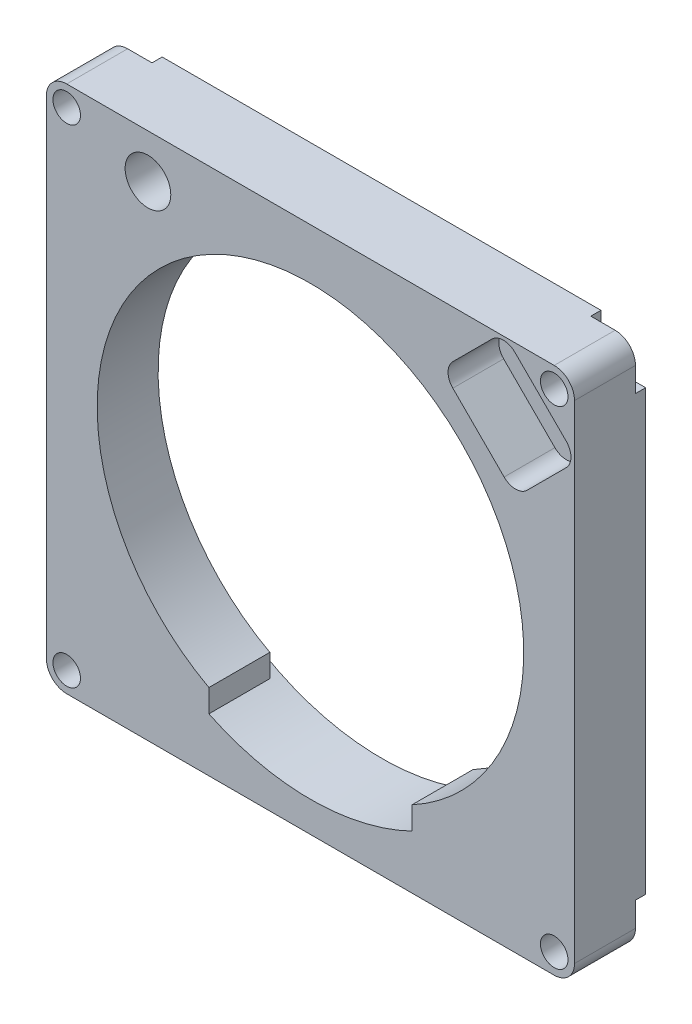
SolidWorks part; units mm, degrees
material "PET"
ref_plane "Front Plane" through (0, 0, 0) normal (0, 0, 1) x (1, 0, 0)
ref_plane "Top Plane" through (0, 0, 0) normal (0, 1, 0) x (1, 0, 0)
ref_plane "Right Plane" through (0, 0, 0) normal (1, 0, 0) x (0, 0, -1)
sketch "Sketch1" plane through (0, 0, 0) normal (0, 0, 1) x (1, 0, 0)
  line L4 (-38.1, -41.275) -> (38.1, -41.275)
  line L5 (41.275, -38.1) -> (41.275, 38.1)
  line L6 (38.1, 41.275) -> (-38.1, 41.275)
  line L7 (-41.275, 38.1) -> (-41.275, -38.1)
  line L8 (-38.1, -41.275) -> (38.1, -41.275)
  line L9 (41.275, -38.1) -> (41.275, 38.1)
  line L10 (38.1, 41.275) -> (-38.1, 41.275)
  line L11 (-41.275, 38.1) -> (-41.275, -38.1)
  line L388 (15.875, -29.3151) -> (15.875, -32.8808) construction
  line L389 (-15.875, -32.8808) -> (-15.875, -29.3151) construction
  line L390 (15.875, -29.3151) -> (15.875, -32.8808)
  line L391 (-15.875, -32.8808) -> (-15.875, -29.3151)
  arc A4 (-41.275, -38.1) -> (-38.1, -41.275) centre (-38.1, -38.1) ccw
  arc A5 (38.1, -41.275) -> (41.275, -38.1) centre (38.1, -38.1) ccw
  arc A6 (41.275, 38.1) -> (38.1, 41.275) centre (38.1, 38.1) ccw
  arc A7 (-38.1, 41.275) -> (-41.275, 38.1) centre (-38.1, 38.1) ccw
  arc A8 (-41.275, -38.1) -> (-38.1, -41.275) centre (-38.1, -38.1) ccw
  arc A9 (38.1, -41.275) -> (41.275, -38.1) centre (38.1, -38.1) ccw
  arc A10 (41.275, 38.1) -> (38.1, 41.275) centre (38.1, 38.1) ccw
  arc A11 (-38.1, 41.275) -> (-41.275, 38.1) centre (-38.1, 38.1) ccw
  arc A388 (15.875, -29.3151) -> (-15.875, -29.3151) centre (0, 0) ccw construction
  arc A389 (-15.875, -32.8808) -> (15.875, -32.8808) centre (0, 0) ccw construction
  arc A390 (15.875, -29.3151) -> (-15.875, -29.3151) centre (0, 0) ccw
  arc A391 (-15.875, -32.8808) -> (15.875, -32.8808) centre (0, 0) ccw
  dimension "D1" = 0
extrude "Boss-Extrude1" add sketch "Sketch1" against normal up to surface (7.9375 mm away)
sketch "Sketch2" plane through (0, 0, -7.9375) normal (0, 0, -1) x (-1, 0, 0)
  line L12 (-34.29, -38.1) -> (-34.29, -41.275)
  line L13 (-34.29, -41.275) -> (34.29, -41.275)
  line L14 (34.29, -41.275) -> (34.29, -38.1)
  line L15 (38.1, -34.29) -> (41.275, -34.29)
  line L16 (41.275, -34.29) -> (41.275, 34.29)
  line L17 (41.275, 34.29) -> (38.1, 34.29)
  line L18 (34.29, 38.1) -> (34.29, 41.275)
  line L19 (34.29, 41.275) -> (-34.29, 41.275)
  line L20 (-34.29, 41.275) -> (-34.29, 38.1)
  line L21 (-38.1, 34.29) -> (-41.275, 34.29)
  line L22 (-41.275, 34.29) -> (-41.275, -34.29)
  line L23 (-41.275, -34.29) -> (-38.1, -34.29)
  line L24 (-34.29, -38.1) -> (-34.29, -41.275)
  line L25 (-34.29, -41.275) -> (34.29, -41.275)
  line L26 (34.29, -41.275) -> (34.29, -38.1)
  line L27 (38.1, -34.29) -> (41.275, -34.29)
  line L28 (41.275, -34.29) -> (41.275, 34.29)
  line L29 (41.275, 34.29) -> (38.1, 34.29)
  line L30 (34.29, 38.1) -> (34.29, 41.275)
  line L31 (34.29, 41.275) -> (-34.29, 41.275)
  line L32 (-34.29, 41.275) -> (-34.29, 38.1)
  line L33 (-38.1, 34.29) -> (-41.275, 34.29)
  line L34 (-41.275, 34.29) -> (-41.275, -34.29)
  line L35 (-41.275, -34.29) -> (-38.1, -34.29)
  circle A0 centre (0, 0) radius 36.5125 construction
  circle A1 centre (0, 0) radius 36.5125
  arc A4 (-34.29, -38.1) -> (-38.1, -34.29) centre (-38.1, -38.1) ccw
  arc A5 (38.1, -34.29) -> (34.29, -38.1) centre (38.1, -38.1) ccw
  arc A6 (34.29, 38.1) -> (38.1, 34.29) centre (38.1, 38.1) ccw
  arc A7 (-38.1, 34.29) -> (-34.29, 38.1) centre (-38.1, 38.1) ccw
  arc A8 (-34.29, -38.1) -> (-38.1, -34.29) centre (-38.1, -38.1) ccw
  arc A9 (38.1, -34.29) -> (34.29, -38.1) centre (38.1, -38.1) ccw
  arc A10 (34.29, 38.1) -> (38.1, 34.29) centre (38.1, 38.1) ccw
  arc A11 (-38.1, 34.29) -> (-34.29, 38.1) centre (-38.1, 38.1) ccw
  dimension "D1" = 0
extrude "Boss-Extrude2" add sketch "Sketch2" along normal blind 1.5875
hole_wizard "#6 Clearance Hole1" positions "Sketch4" profile "Sketch3" hole size "#6" standard "ANSI Inch" end condition through all
sketch "Sketch4" plane through (0, 0, -7.9375) normal (0, 0, -1) x (-1, 0, 0)
  point P0 (-38.1, 38.1)
  point P3 (38.1, 38.1)
  point P6 (38.1, -38.1)
  point P9 (-38.1, -38.1)
sketch "Sketch3" plane through (38.1, 38.1, -7.9375) normal (1, 0, 0) x (0, 1, 0)
  line L0 (0, 0) -> (0, 7.9375)
  line L1 (0, 7.9375) -> (2.1526, 7.9375)
  line L2 (2.1526, 7.9375) -> (2.1526, 0)
  line L5 (2.1526, 0) -> (0, 0)
  line L11 (0, -6.35) -> (0, 107.95) construction
  dimension "Thru Hole Dia." = 4.3053
  dimension "Thru Hole Depth" = 7.9375
sketch "Sketch5" plane through (0, 0, 0) normal (0, 0, 1) x (1, 0, 0)
  circle A0 centre (-25.4, 34.417) radius 3.5712
  dimension "D1" = 7.1425
extrude "Cut-Extrude1" cut sketch "Sketch5" against normal offset from surface (7.9375 mm away) 1.5875 up to face at (0, 0, -9.525)
sketch "Sketch6" plane through (0, 0, -7.9375) normal (0, 0, 1) x (1, 0, 0)
  circle A0 centre (-25.4, 34.417) radius 2.1
  dimension "D1" = 4.2
extrude "Cut-Extrude2" cut sketch "Sketch6" against normal up to next
sketch "Sketch7" plane through (0, 0, 0) normal (0, 0, 1) x (1, 0, 0)
  line L0 (22.255, 30.2707) -> (30.2707, 22.255)
  line L1 (22.255, 33.8628) -> (28.3672, 39.975)
  line L2 (33.8628, 22.255) -> (39.975, 28.3672)
  line L3 (31.9593, 39.975) -> (39.975, 31.9593)
  line L4 (20.4589, 32.0668) -> (41.7711, 30.1632) construction
  line L5 (32.0668, 20.4589) -> (30.1632, 41.7711) construction
  line L6 (24.0439, 34.9334) -> (23.7611, 34.6505) construction
  line L7 (25.246, 28.3573) -> (24.5389, 29.0644) construction
  arc A0 (28.3672, 39.975) -> (31.9593, 39.975) centre (30.1632, 38.179) cw
  arc A1 (39.975, 28.3672) -> (39.975, 31.9593) centre (38.179, 30.1632) ccw
  arc A2 (30.2707, 22.255) -> (33.8628, 22.255) centre (32.0668, 24.051) ccw
  arc A3 (22.255, 33.8628) -> (22.255, 30.2707) centre (24.051, 32.0668) ccw
  point P1 (31.115, 31.115)
  dimension "D3" = 2.54
  dimension "D1" = 0.508
  dimension "D2" = 0.762
extrude "Cut-Extrude3" cut sketch "Sketch7" against normal offset from surface (6.35 mm away) 3.175 up to face at (-27.5, 34.417, -9.525)
hole_wizard "5/16 Clearance Hole1" positions "Sketch9" profile "Sketch8" hole size "5/16" standard "ANSI Inch" end condition through all
sketch "Sketch9" plane through (0, 0, -9.525) normal (0, 0, -1) x (-1, 0, 0)
  point P0 (-31.115, 31.115)
sketch "Sketch8" plane through (31.115, 31.115, -9.525) normal (1, 0, 0) x (0, 1, 0)
  line L0 (0, 0) -> (0, 9.525)
  line L1 (0, 9.525) -> (4.1021, 9.525)
  line L2 (4.1021, 9.525) -> (4.1021, 0)
  line L5 (4.1021, 0) -> (0, 0)
  line L11 (0, -6.35) -> (0, 107.95) construction
  dimension "Thru Hole Dia." = 8.2042
  dimension "Thru Hole Depth" = 9.525
sketch "Sketch10" plane through (0, 0, 0) normal (0, 0, 1) x (1, 0, 0)
  line L2 (15.875, -32.8808) -> (15.875, -29.3151)
  line L3 (-15.875, -29.3151) -> (-15.875, -32.8808)
  line L4 (-38.1, -41.275) -> (38.1, -41.275)
  line L5 (41.275, -38.1) -> (41.275, 38.1)
  line L6 (38.1, 41.275) -> (-38.1, 41.275)
  line L7 (-41.275, 38.1) -> (-41.275, -38.1)
  line L8 (-38.1, -41.275) -> (38.1, -41.275)
  line L9 (41.275, -38.1) -> (41.275, 38.1)
  line L10 (38.1, 41.275) -> (-38.1, 41.275)
  line L11 (-41.275, 38.1) -> (-41.275, -38.1)
  line L12 (15.875, -32.8808) -> (15.875, -29.3151)
  line L13 (-15.875, -29.3151) -> (-15.875, -32.8808)
  line L17 (28.3672, 39.975) -> (22.255, 33.8628)
  line L18 (39.975, 31.9593) -> (31.9593, 39.975)
  line L19 (33.8628, 22.255) -> (39.975, 28.3672)
  line L20 (22.255, 30.2707) -> (30.2707, 22.255)
  line L21 (28.3672, 39.975) -> (22.255, 33.8628)
  line L22 (39.975, 31.9593) -> (31.9593, 39.975)
  line L23 (33.8628, 22.255) -> (39.975, 28.3672)
  line L24 (22.255, 30.2707) -> (30.2707, 22.255)
  circle A1 centre (-25.4, 34.417) radius 3.5712 construction
  circle A2 centre (-38.1, 38.1) radius 2.1526 construction
  arc A3 (15.875, -29.3151) -> (-15.875, -29.3151) centre (0, 0) ccw
  arc A4 (-41.275, -38.1) -> (-38.1, -41.275) centre (-38.1, -38.1) ccw
  arc A5 (38.1, -41.275) -> (41.275, -38.1) centre (38.1, -38.1) ccw
  arc A6 (41.275, 38.1) -> (38.1, 41.275) centre (38.1, 38.1) ccw
  arc A7 (-38.1, 41.275) -> (-41.275, 38.1) centre (-38.1, 38.1) ccw
  arc A8 (-41.275, -38.1) -> (-38.1, -41.275) centre (-38.1, -38.1) ccw
  arc A9 (38.1, -41.275) -> (41.275, -38.1) centre (38.1, -38.1) ccw
  arc A10 (41.275, 38.1) -> (38.1, 41.275) centre (38.1, 38.1) ccw
  arc A11 (-38.1, 41.275) -> (-41.275, 38.1) centre (-38.1, 38.1) ccw
  arc A12 (-15.875, -32.8808) -> (15.875, -32.8808) centre (0, 0) ccw
  arc A13 (15.875, -29.3151) -> (-15.875, -29.3151) centre (0, 0) ccw
  arc A14 (-15.875, -32.8808) -> (15.875, -32.8808) centre (0, 0) ccw
  circle A15 centre (-38.1, -38.1) radius 2.1526 construction
  circle A16 centre (38.1, -38.1) radius 2.1526 construction
  circle A17 centre (38.1, 38.1) radius 2.1526 construction
  circle A18 centre (38.1, 38.1) radius 2.1526
  circle A19 centre (38.1, -38.1) radius 2.1526
  circle A20 centre (-38.1, -38.1) radius 2.1526
  circle A21 centre (-38.1, 38.1) radius 2.1526
  arc A22 (31.9593, 39.975) -> (28.3672, 39.975) centre (30.1632, 38.179) ccw
  arc A23 (39.975, 28.3672) -> (39.975, 31.9593) centre (38.179, 30.1632) ccw
  arc A24 (30.2707, 22.255) -> (33.8628, 22.255) centre (32.0668, 24.051) ccw
  arc A25 (22.255, 33.8628) -> (22.255, 30.2707) centre (24.051, 32.0668) ccw
  arc A26 (31.9593, 39.975) -> (28.3672, 39.975) centre (30.1632, 38.179) ccw
  arc A27 (39.975, 28.3672) -> (39.975, 31.9593) centre (38.179, 30.1632) ccw
  arc A28 (30.2707, 22.255) -> (33.8628, 22.255) centre (32.0668, 24.051) ccw
  arc A29 (22.255, 33.8628) -> (22.255, 30.2707) centre (24.051, 32.0668) ccw
  circle A30 centre (-25.4, 34.417) radius 3.5712
  dimension "D1" = 0
  dimension "D2" = 0
  dimension "D3" = 0
extrude "Boss-Extrude3" add sketch "Sketch10" along normal blind 1.5875
